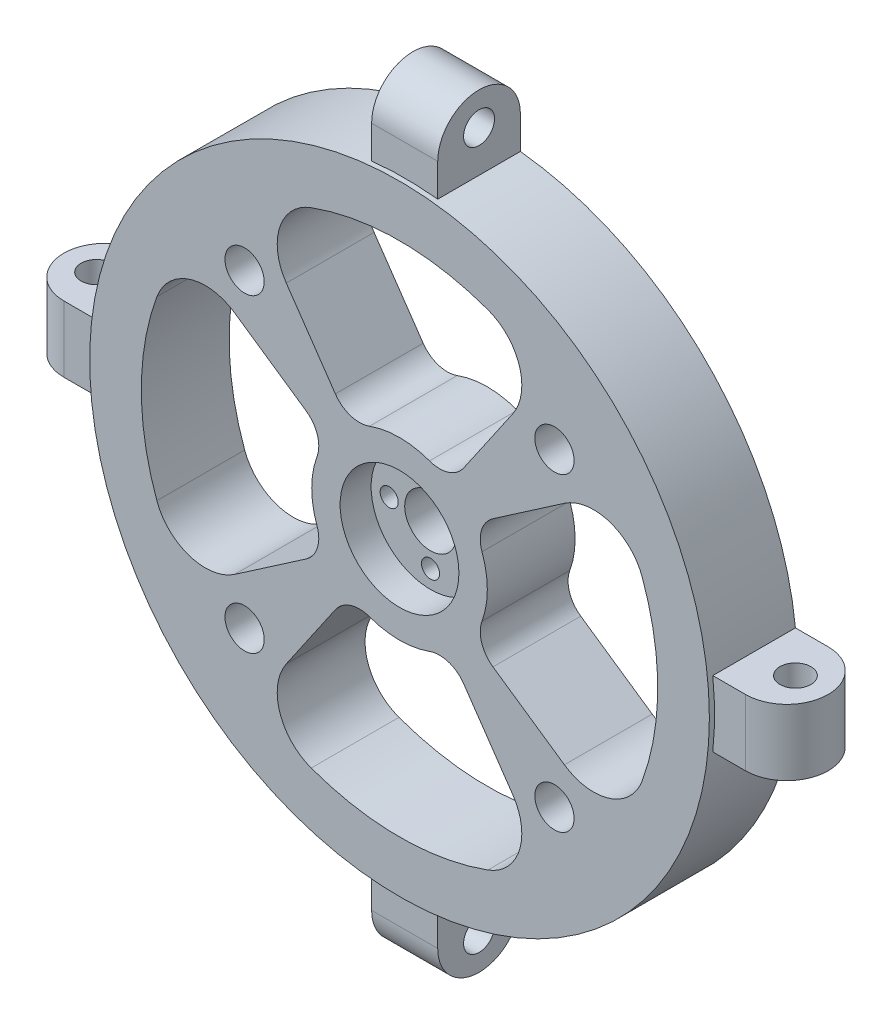
SolidWorks part; units mm, degrees
material "尼龙 101"
ref_plane "前视基准面" through (0, 0, 0) normal (0, 0, 1) x (1, 0, 0)
ref_plane "上视基准面" through (0, 0, 0) normal (0, 1, 0) x (1, 0, 0)
ref_plane "右视基准面" through (0, 0, 0) normal (1, 0, 0) x (0, 0, -1)
sketch "草图1" plane through (0, 0, 0) normal (0, 0, 1) x (1, 0, 0)
  circle A0 centre (0, 0) radius 60
  dimension "D1" = 120
extrude "凸台-拉伸1" add sketch "草图1" along normal blind 17
sketch "草图2" plane through (0, 0, 17) normal (0, 0, 1) x (1, 0, 0)
  line L0 (0, 30) -> (0, 0) construction
  line L1 (0, 0) -> (0, -30) construction
  line L2 (-30, 0) -> (0, 0) construction
  line L3 (0, 0) -> (30, 0) construction
  circle A4 centre (-30, 30) radius 3.8
  circle A5 centre (30, 30) radius 3.8
  circle A6 centre (30, -30) radius 3.8
  circle A7 centre (-30, -30) radius 3.8
  dimension "D1" = 7.6
  dimension "D2" = 7.6
  dimension "D7" = 7.6
  dimension "D8" = 7.6
  dimension "D3" = 30
  dimension "D4" = 30
  dimension "D5" = 30
  dimension "D6" = 30
  dimension "D9" = 60
  dimension "D10" = 60
extrude "切除-拉伸1" cut sketch "草图2" against normal through all
sketch "草图3" plane through (0, 0, 0) normal (1, 0, 0) x (0, 0, -1)
  line L0 (0, 58) -> (-16, 58)
  line L1 (-16, 58) -> (-16, 66)
  line L2 (0, 66) -> (0, 58)
  line L3 (0, 0) -> (-35.6052, 0) construction
  arc A0 (-16, 66) -> (0, 66) centre (-8, 66) cw
  dimension "D3" = 8
  dimension "D1" = 58
  dimension "D2" = 8
  dimension "D4" = 0
extrude "凸台-拉伸2" add sketch "草图3" along normal blind 6.4 and the other way blind 6.4
sketch "草图4" plane through (6.4, 0, 0) normal (1, 0, 0) x (0, 0, -1)
  line L0 (-16, 59.6577) -> (0, 59.6577) construction
  line L1 (0, 59.6577) -> (0, 66) construction
  circle A0 centre (-8, 67.6577) radius 3
  dimension "D1" = 6
  dimension "D2" = 8
  dimension "D3" = 8
extrude "切除-拉伸7" cut sketch "草图4" against normal through all
sketch "草图5" plane through (0, 0, 0) normal (0, 0, -1) x (-1, 0, 0)
  circle A0 centre (0, 0) radius 5
  dimension "D1" = 10
extrude "切除-拉伸3" cut sketch "草图5" against normal up to next
sketch "草图6" plane through (0, 0, 17) normal (0, 0, 1) x (1, 0, 0)
  circle A0 centre (0, 0) radius 11.5
  dimension "D1" = 23
extrude "切除-拉伸4" cut sketch "草图6" against normal blind 6
sketch "草图7" plane through (0, 0, 11) normal (0, 0, 1) x (1, 0, 0)
  circle A0 centre (0, 0) radius 8 construction
  circle A1 centre (-8, 0) radius 1.75
  circle A2 centre (0, 8) radius 1.75
  circle A3 centre (8, 0) radius 1.75
  circle A4 centre (0, -8) radius 1.75
  dimension "D1" = 16
  dimension "D2" = 3.5
  dimension "D3" = 3.5
  dimension "D4" = 3.5
  dimension "D5" = 3.5
extrude "切除-拉伸5" cut sketch "草图7" against normal up to next
sketch "草图8" plane through (0, 0, 17) normal (0, 0, 1) x (1, 0, 0)
  line L0 (-37.5877, -13.6808) -> (0, 0) construction
  line L1 (0, 0) -> (-37.5877, 13.6808) construction
  line L2 (0, 0) -> (-30, 0) construction
  line L3 (-37.5877, -13.6808) -> (-46.9846, -17.101) construction
  line L4 (-37.5877, 13.6808) -> (-46.9846, 17.101) construction
  line L13 (-18.0919, -12.4238) -> (0, 0) construction
  line L14 (-18.0919, 12.4238) -> (-31.9269, 21.9243)
  line L15 (-31.9269, -21.9243) -> (-18.0919, -12.4238)
  arc A0 (-37.5877, -13.6808) -> (-37.5877, 13.6808) centre (0, 0) cw construction
  arc A6 (-46.9846, -17.101) -> (-46.9846, 17.101) centre (0, 0) cw
  arc A7 (-46.9846, -17.101) -> (-31.9269, -21.9243) centre (-37.5877, -13.6808) ccw
  arc A9 (-15.9748, -5.8143) -> (-15.9748, 5.8143) centre (0, 0) cw
  arc A11 (-15.9748, -5.8143) -> (-18.0919, -12.4238) centre (-21.2997, -7.7525) cw
  arc A31 (-15.9748, 5.8143) -> (-18.0919, 12.4238) centre (-21.2997, 7.7525) ccw
  arc A32 (-46.9846, 17.101) -> (-31.9269, 21.9243) centre (-37.5877, 13.6808) cw
  dimension "D2" = 20
  dimension "D3" = 40
  dimension "D4" = 50
  dimension "D5" = 17
extrude "切除-拉伸6" cut sketch "草图8" against normal up to next
pattern_circular "阵列(圆周)3" count 4 over 360 about axis through (0, 0, 17) along (0, 0, 1) of "切除-拉伸6"
pattern_circular "阵列(圆周)4" count 4 over 360 about axis through (0, 0, 17) along (0, 0, 1) of "凸台-拉伸2", "切除-拉伸7"
